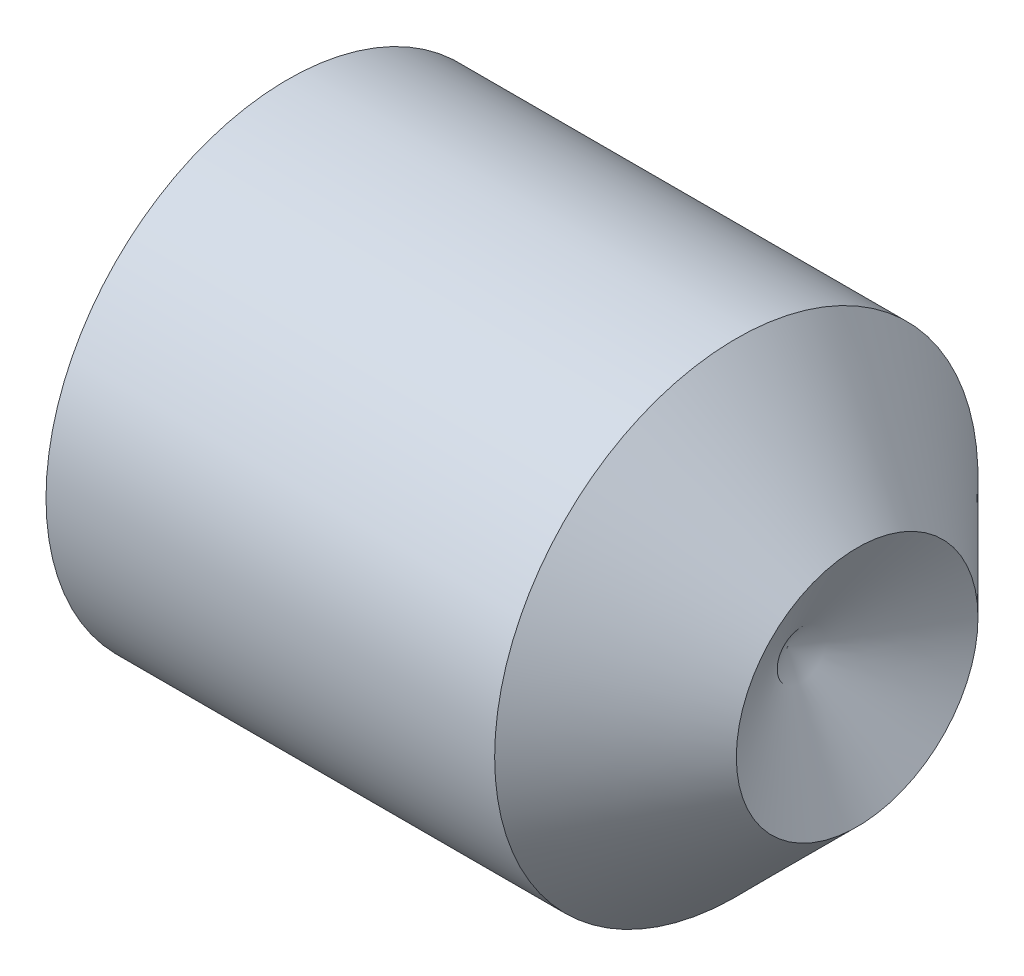
SolidWorks part; units mm, degrees
ref_plane "Front Plane" through (0, 0, 0) normal (0, 0, 1) x (1, 0, 0)
ref_plane "Top Plane" through (0, 0, 0) normal (0, 1, 0) x (1, 0, 0)
ref_plane "Right Plane" through (0, 0, 0) normal (1, 0, 0) x (0, 0, -1)
sketch "BodySke" plane through (0, 0, 0) normal (0, 0, 1) x (1, 0, 0)
  line L0 (0, 0) -> (3.28, 0) construction
  line L1 (2, 0) -> (2, 0.4)
  line L2 (2, 0.4) -> (1.6, 0.8)
  line L3 (1.6, 0.8) -> (0, 0.8)
  line L4 (0, 0.8) -> (0, 0)
  line L5 (0, 0) -> (2, 0)
  line L6 (1.65, 1.0236) -> (1.65, -0.6432) construction
  point P5 (0, 0.601)
  dimension "Minor_dia" = 1.202
  dimension "Advance" = 0.35
revolve "BaseBody" add sketch "BodySke" angle 360 about L0
cosmetic thread "ThreadCosmetic" [suppressed] parameters "Minor_dia"=1.202
sketch "HeadChamferSke" plane through (0, 0, 0) normal (0, 0, 1) x (1, 0, 0)
  line L0 (0, 0) -> (2.4505, 0) construction
  line L1 (0, 0.8) -> (0, 0.601)
  line L2 (0, 0.8) -> (0.1149, 0.8)
  line L3 (0.1149, 0.8) -> (0, 0.601)
  line L4 (1.6, 0.8) -> (0, 0.8) construction
  line L5 (0, 0.8) -> (0, -0.8) construction
  line L6 (0, 0.8) -> (0, 0) construction
  dimension "Angle" = 30
revolve "HeadChamfer" cut sketch "HeadChamferSke" angle 360 about L0
sketch "HexagonSocketSke" plane through (0, 0, 0) normal (-1, 0, 0) x (0, 0, 1)
  line L1 (0, 0.4041) -> (-0.35, 0.2021)
  line L2 (-0.35, 0.2021) -> (-0.35, -0.2021)
  line L3 (-0.35, -0.2021) -> (0, -0.4041)
  line L4 (0, -0.4041) -> (0.35, -0.2021)
  line L5 (0.35, -0.2021) -> (0.35, 0.2021)
  line L6 (0.35, 0.2021) -> (0, 0.4041)
  circle A0 centre (0, 0) radius 0.35 construction
  dimension "Hexagon_Width" = 0.7
extrude "HexagonSocket" cut sketch "HexagonSocketSke" against normal blind 0.7
sketch "CupPointSke" plane through (0, 0, 0) normal (0, 0, 1) x (1, 0, 0)
  line L0 (0, 0) -> (2.5104, 0) construction
  line L1 (2, 0.4) -> (2, 0)
  line L2 (2, 0) -> (1.7691, 0)
  line L3 (1.7691, 0) -> (2, 0.4)
  dimension "D1" = 60
revolve "CupPoint" cut sketch "CupPointSke" angle 360 about L0
sketch "ThdSchSke" plane through (0, 0, 0) normal (0, 0, 1) x (1, 0, 0)
  line L0 (0, 0) -> (2.6881, 0) construction
  line L1 (0.2351, 1.0298) -> (0.2351, 0.8)
  line L2 (0.2351, 1.0298) -> (0.4649, 1.0298)
  line L3 (0.4649, 1.0298) -> (0.4649, 0.8)
  line L4 (0.4649, 0.8) -> (0.35, 0.601)
  line L5 (0.35, 0.601) -> (0.2351, 0.8)
  line L6 (1.6, 0.8) -> (0.1149, 0.8) construction
  dimension "D1" = 0.35
revolve "ThreadSchematic" [suppressed] cut sketch "ThdSchSke" angle 360 about L0
pattern_linear "ThdSchPat" [suppressed] count 4 along (1, 0, 0) of bodies 104
equation "\"Minor_dia@ThreadCosmetic\" = \"Minor_dia@BodySke\""
equation "\"D1@ThdSchSke\" = \"Advance@BodySke\""
equation "\"Advance@ThdSchPat\" = \"Advance@BodySke\""
equation "\"D1@ThdSchPat\" =  int(  ( \"Length@BodySke\" -  ( \"Diameter@BodySke\" / 2 - \"Chamfer_End@BodySke\" / 2 )  )  / \"Advance@BodySke\" * 0.99 )"
